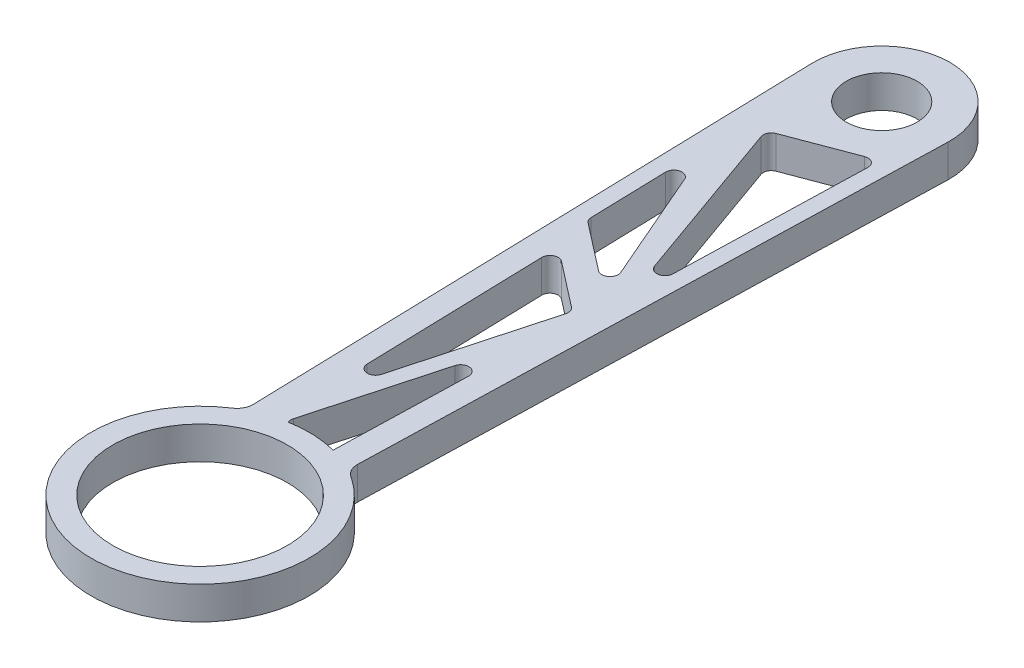
SolidWorks part; units mm, degrees
material "1060 合金"
ref_plane "前视基准面" through (0, 0, 0) normal (0, 0, 1) x (1, 0, 0)
ref_plane "上视基准面" through (0, 0, 0) normal (0, 1, 0) x (1, 0, 0)
ref_plane "右视基准面" through (0, 0, 0) normal (1, 0, 0) x (0, 0, -1)
sketch "草图1" plane through (0, 0, 0) normal (0, 1, 0) x (1, 0, 0)
  line L0 (0, 0) -> (0, 250) construction
  line L1 (-17.9929, -0.504) -> (-24.9902, 249.3)
  line L2 (17.9929, -0.504) -> (24.9902, 249.3)
  line L3 (-11.9953, -0.336) -> (-18.9926, 249.468) construction
  line L4 (11.9953, -0.336) -> (18.9926, 249.468) construction
  line L5 (-16.4444, 158.5) -> (15.7446, 133.5146) construction
  line L6 (15.7446, 133.5146) -> (18.4752, 231) construction
  line L7 (18.4752, 231) -> (-18.0888, 217.2024) construction
  line L8 (-18.0888, 217.2024) -> (-16.4444, 158.5) construction
  line L9 (15.7446, 133.5146) -> (-18.0888, 217.2024) construction
  line L10 (18.5259, 134.639) -> (-15.3075, 218.3268) construction
  line L11 (12.9633, 132.3901) -> (-20.8701, 216.0779) construction
  line L12 (-16.4444, 158.5) -> (-17.7049, 203.5)
  line L13 (-17.7049, 203.5) -> (11.0289, 137.1749)
  line L14 (11.0289, 137.1749) -> (-16.4444, 158.5)
  line L15 (15.9543, 141) -> (18.4752, 231)
  line L16 (-15.3075, 218.3268) -> (-18.4322, 226.0559) construction
  line L17 (18.4752, 231) -> (-12, 219.5)
  line L18 (-12, 219.5) -> (15.9543, 141)
  circle A0 centre (0, 250) radius 25 construction
  circle A1 centre (0, 0) radius 18 construction
  circle A2 centre (0, 0) radius 5.05
  circle A3 centre (0, 250) radius 13
  arc A4 (-17.9929, -0.504) -> (17.9929, -0.504) centre (0, 0) ccw
  arc A5 (-24.9902, 249.3) -> (24.9902, 249.3) centre (0, 250) cw
  arc A6 (-18.9926, 249.468) -> (18.9926, 249.468) centre (0, 250) cw construction
  arc A7 (-11.9953, -0.336) -> (11.9953, -0.336) centre (0, 0) ccw construction
  dimension "D2" = 50
  dimension "D3" = 36
  dimension "D4" = 10.1
  dimension "D5" = 26
  dimension "D1" = 250
  dimension "D9" = 19
  dimension "D10" = 30.5
  dimension "D11" = 16
  dimension "D12" = 45
  dimension "D13" = 90
  dimension "D14" = 12
  dimension "D6" = 6
  dimension "D7" = 3
  dimension "D8" = 3
extrude "凸台-拉伸1" add sketch "草图1" along normal blind 12
fillet "圆角1" radius 3 6 edges at (18.4752, 6, -231) (-12, 6, -219.5) (-17.7049, 6, -203.5) (-16.4444, 6, -158.5) (15.9543, 6, -141) (11.0289, 6, -137.1749)
sketch "草图2" plane through (0, 12, 0) normal (0, 1, 0) x (1, 0, 0)
  line L0 (0, 250) -> (-15, 250) construction
  circle A0 centre (-15, 250) radius 2
  dimension "D2" = 4
  dimension "D1" = 15
extrude "切除-拉伸1" [suppressed] cut sketch "草图2" against normal through all
pattern_circular "阵列(圆周)1" [suppressed] count 3 over 360 reverse direction yes of bodies 107
sketch "草图3" plane through (0, 12, 0) normal (0, 1, 0) x (1, 0, 0)
  line L0 (0, 250) -> (14.25, 250) construction
  circle A0 centre (14.25, 250) radius 2
  dimension "D2" = 4
  dimension "D1" = 14.25
extrude "切除-拉伸2" [suppressed] cut sketch "草图3" against normal through all
pattern_circular "阵列(圆周)2" [suppressed] count 3 over 360 of bodies 109
sketch "草图4" plane through (0, 12, 0) normal (0, 1, 0) x (1, 0, 0)
  line L2 (8.9965, -0.252) -> (15.9937, 249.552)
  line L3 (8.9965, -0.252) -> (15.9937, 249.552) construction
  line L4 (-13.0503, 144.4724) -> (12.4949, 124.6439)
  line L5 (-15.9937, 249.552) -> (-8.9965, -0.252)
  line L6 (-15.9937, 249.552) -> (-8.9965, -0.252) construction
  line L7 (-15.3248, 157.6309) -> (1.7846, 144.3504) construction
  line L8 (12.4949, 124.6439) -> (9.7421, 26.3657)
  line L9 (9.7421, 26.3657) -> (-10.1751, 41.8256)
  line L10 (-10.1751, 41.8256) -> (-13.0503, 144.4724)
  dimension "D3" = 9
  dimension "D1" = 9
  dimension "D2" = 9
extrude "切除-拉伸3" cut sketch "草图4" against normal through all
fillet "圆角2" radius 3 3 edges at (9.7421, 6, -26.3657) (-10.1751, 6, -41.8256) (-13.0503, 6, -144.4724)
sketch "草图5" plane through (0, 12, 0) normal (0, 1, 0) x (1, 0, 0)
  circle A0 centre (0, 0) radius 40
  circle A1 centre (0, 0) radius 5.05
  dimension "D1" = 80
extrude "凸台-拉伸2" add sketch "草图5" against normal up to surface (12 mm away) up to face at (-1.8624, 0, -78.5335)
fillet "圆角3" radius 6 2 edges at (-18.9931, 6, -35.2031) (18.9931, 6, -35.2031)
sketch "草图6" plane through (0, 12, 0) normal (0, 1, 0) x (1, 0, 0)
  line L0 (12.4949, 124.6439) -> (-10.1751, 41.8256) construction
  line L1 (-12.8725, 138.1249) -> (-10.2148, 43.2424) construction
  line L2 (9.6014, 125.4359) -> (-13.0687, 42.6176)
  line L3 (15.3885, 123.8518) -> (-7.2816, 41.0335)
  line L4 (-7.2816, 41.0335) -> (-7.6098, 39.8344)
  line L5 (-7.6098, 39.8344) -> (-13.0687, 42.6176)
  line L6 (9.6014, 125.4359) -> (9.9296, 126.6351)
  line L7 (9.9296, 126.6351) -> (15.3885, 123.8518)
  line L8 (-9.0555, 40.9565) -> (-7.0227, 39.3787) construction
  line L9 (12.4949, 124.6439) -> (-8.0342, 140.5788) construction
  dimension "D1" = 3
  dimension "D2" = 3
extrude "凸台-拉伸3" add sketch "草图6" against normal up to surface (12 mm away) up to face at (-3.6592, 0, -81.1373)
fillet "圆角4" radius 3 4 edges at (12.1404, 6, -111.9858) (-10.4638, 6, -52.1336) (9.9296, 6, -126.6351) (-7.6098, 6, -39.8344)
sketch "草图7" plane through (0, 12, 0) normal (0, 1, 0) x (1, 0, 0)
  line L1 (15, 15) -> (-15, 15) construction
  line L2 (15, 15) -> (15, -15) construction
  line L3 (15, -15) -> (-15, -15) construction
  line L4 (-15, 15) -> (-15, -15) construction
  circle A0 centre (0, 0) radius 5.05 construction
  circle A1 centre (15, 15) radius 2.05
  circle A2 centre (-15, 15) radius 2.05
  circle A3 centre (-15, -15) radius 2.05
  circle A5 centre (15, -15) radius 2.05
  dimension "D2" = 15
  dimension "D4" = 4.1
  dimension "D1" = 30
  dimension "D3" = 15
sketch "草图8" plane through (0, 12, 0) normal (0, 1, 0) x (1, 0, 0)
  circle A0 centre (0, 0) radius 32
  dimension "D1" = 64
extrude "切除-拉伸5" cut sketch "草图8" against normal through all
